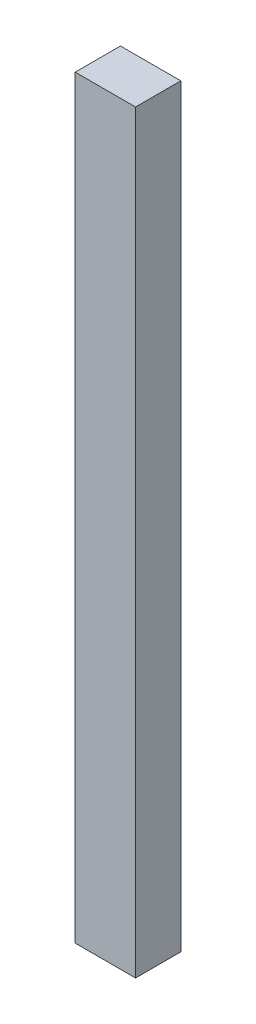
SolidWorks part; units mm, degrees
material "Stainless Steel (ferritic)"
ref_plane "Front Plane" through (0, 0, 0) normal (0, 0, 1) x (1, 0, 0)
ref_plane "Top Plane" through (0, 0, 0) normal (0, 1, 0) x (1, 0, 0)
ref_plane "Right Plane" through (0, 0, 0) normal (1, 0, 0) x (0, 0, -1)
sketch "Sketch1" plane through (0, 0, 0) normal (0, 0, 1) x (1, 0, 0)
  line L1 (-20, -250) -> (20, -250)
  line L2 (-20, -250) -> (-20, 250)
  line L3 (-20, 250) -> (20, 250)
  line L4 (20, -250) -> (20, 250)
  line L5 (-20, -250) -> (20, 250) construction
  line L6 (-20, 250) -> (20, -250) construction
  point P0 (0, 0)
  dimension "D1" = 40
  dimension "D2" = 500
extrude "Boss-Extrude1" add sketch "Sketch1" along normal blind 30
sketch "Sketch2" plane through (0, 0, 30) normal (0, 0, 1) x (1, 0, 0)
  line L0 (0, 250) -> (20, 250) construction
  line L1 (20, 250) -> (-20, 250) construction
  line L2 (10, 250) -> (10, -250) construction
  line L3 (-20, -250) -> (20, -250) construction
  line L4 (20, -250) -> (20, 250) construction
  point P8 (10, 200)
  point P9 (10, -200)
  point P10 (10, 100)
  point P11 (10, -100)
  point P12 (10, 0)
  dimension "D1" = 200
  dimension "D2" = 100
  dimension "D3" = 200
  dimension "D4" = 100
  dimension "D5" = 10
